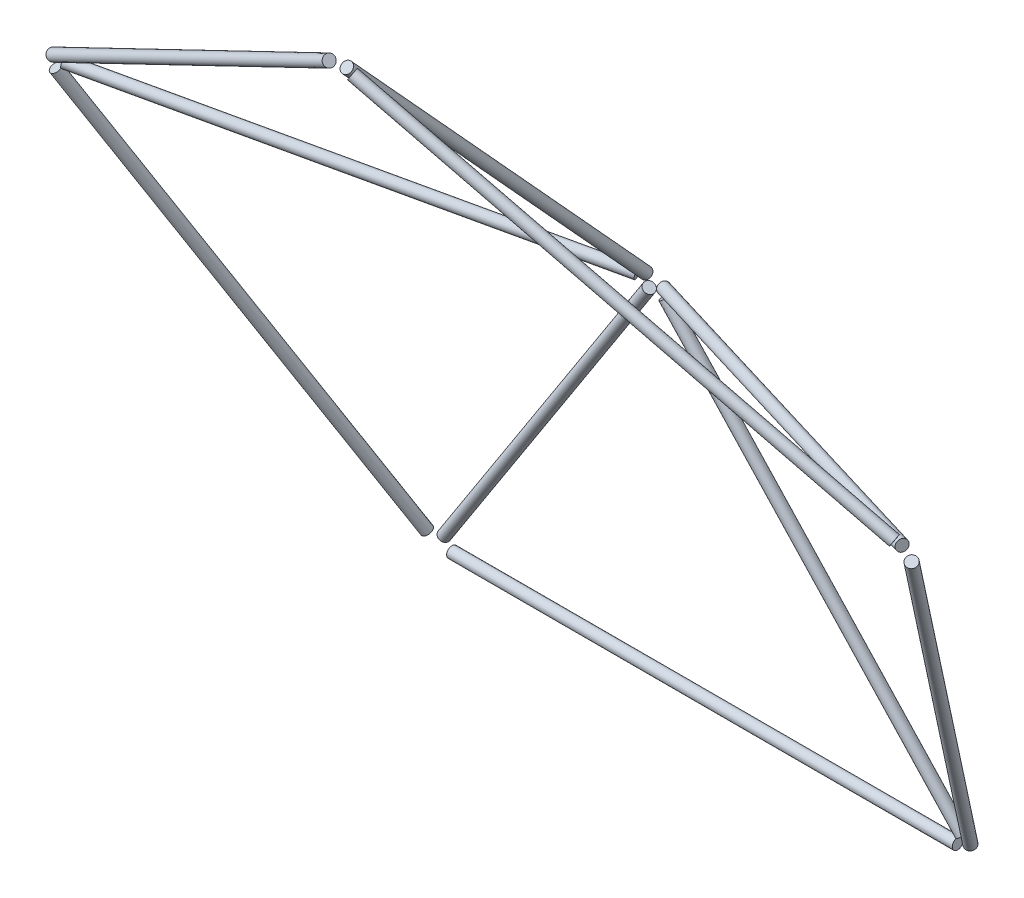
SolidWorks part; units mm, degrees
note: '?' marks a value the reader was unsure of.
ref_plane "Front Plane" through (0, 0, 0) normal (0, 0, 1) x (1, 0, 0)
ref_plane "Top Plane" through (0, 0, 0) normal (0, 1, 0) x (1, 0, 0)
ref_plane "Right Plane" through (0, 0, 0) normal (1, 0, 0) x (0, 0, -1)
sketch "Sketch1" plane through (0, 0, 0) normal (0, 1, 0) x (1, 0, 0)
  line L0 (190.928, 143.4196) -> (77.4001, 225.9024)
  line L1 (194.1641, -141.0685) -> (240, 0) construction
  line L2 (240, 0) -> (194.1641, 141.0685) construction
  line L3 (194.1641, 141.0685) -> (74.1641, 228.2536) construction
  line L4 (74.1641, 228.2536) -> (-74.1641, 228.2536) construction
  line L5 (-74.1641, 228.2536) -> (-194.1641, 141.0685) construction
  line L6 (-194.1641, 141.0685) -> (-240, 0) construction
  line L7 (-240, 0) -> (-194.1641, -141.0685) construction
  line L8 (-194.1641, -141.0685) -> (-74.1641, -228.2536) construction
  line L9 (-74.1641, -228.2536) -> (74.1641, -228.2536) construction
  line L10 (74.1641, -228.2536) -> (194.1641, -141.0685) construction
  line L11 (120, 87.1851) -> (74.1641, 228.2536) construction
  line L12 (74.1641, 228.2536) -> (-74.1641, 228.2536) construction
  line L13 (-74.1641, 228.2536) -> (-120, 87.1851) construction
  line L14 (-120, 87.1851) -> (0, 0) construction
  line L15 (0, 0) -> (120, 87.1851) construction
  line L16 (0, 0) -> (-194.1641, -141.0685) construction
  line L17 (-74.1641, -228.2536) -> (74.1641, 228.2536) construction
  circle A0 centre (0, 0) radius 240 construction
  circle A1 centre (0, 0) radius 228.2536 construction
  circle A2 centre (0, 126.1755) radius 102.0781 construction
  point P16 (0, 240)
  point P24 (0, 228.2536)
  dimension "D1" = 480
  dimension "D2" = 4
  dimension "D3" = 4
sketch "Sketch5" plane through (0, 0, 0) normal (1, 0, 0) x (0, 0, -1)
  line L0 (0, 0) -> (126.1755, 204.1562)
  line L1 (126.1755, 204.1562) -> (228.2536, 0)
  line L2 (182.6029, 91.3014) -> (214.6625, 107.3313) construction
  line L3 (-49.7754, 154.1978) -> (144.5877, 34.0748) construction
  circle A0 centre (228.2536, 0) radius 228.2536 construction
  circle A1 centre (0, 0) radius 240 construction
  circle A2 centre (228.2536, 0) radius 102.0781 construction
  point P0 (228.2536, 0)
  point P8 (126.1755, 204.1562)
ref_plane "Plane1" through (0, 91.3014, -182.6029) normal (0, 0.4472, -0.8944) x (-1, 0, 0)
sketch "Sketch6" plane through (0, 91.3014, -182.6029) normal (0, 0.4472, -0.8944) x (-1, 0, 0)
  line L0 (-74.1641, -102.0781) -> (74.1641, -102.0781) construction
  line L1 (-74.1641, -102.0781) -> (74.1641, -102.0781)
  line L2 (-118.7639, 35.1861) -> (-75.4001, -98.2739)
  line L3 (-74.1641, -102.0781) -> (74.1641, -102.0781)
  line L4 (74.1641, -102.0781) -> (120, 38.9904)
  line L5 (120, 38.9904) -> (0, 126.1755)
  line L6 (0, 126.1755) -> (-120, 38.9904)
  line L7 (-120, 38.9904) -> (-74.1641, -102.0781) construction
  circle A0 centre (0, 0) radius 102.0781 construction
  point P0 (0, 0)
  dimension "D1" = 4
  dimension "D2" = 4
ref_plane "Plane2" through (0, 107.3313, -214.6625) normal (0, 0.4472, -0.8944) x (-1, 0, 0)
sketch "Sketch7" plane through (0, 107.3313, -214.6625) normal (0, 0.4472, -0.8944) x (-1, 0, 0)
  point P0 (0, 0)
ref_plane "Plane7" through (44.0977, 149.8374, -163.9562) normal (0.1947, 0.6617, -0.724) x (-0.9809, 0.1314, -0.1438)
sketch "Sketch15" plane through (44.0977, 149.8374, -163.9562) normal (0.1947, 0.6617, -0.724) x (-0.9809, 0.1314, -0.1438)
  line L0 (-77.3838, -18.2827) -> (44.9584, -65.584)
  line L1 (44.9584, -65.584) -> (44.9584, 65.584)
  line L2 (44.9584, 65.584) -> (-77.3838, -18.2827)
surface "Surface-Plane1" sketch "Sketch15"
ref_plane "Plane8" through (71.3515, 74.814, -201.4679) normal (0.3151, 0.3304, -0.8897) x (-0.9491, 0.1097, -0.2954)
sketch "Sketch16" plane through (71.3515, 74.814, -201.4679) normal (0.3151, 0.3304, -0.8897) x (-0.9491, 0.1097, -0.2954)
  line L0 (-2.9635, -79.459) -> (75.1812, 25.8901) construction
  line L1 (72.7982, 22.6774) -> (-0.5805, -76.2463)
  dimension "D1" = 4
  dimension "D2" = 4
ref_axis "Axis2" through (0, 91.3014, -182.6029) along (0, 0.4472, -0.8944)?
ref_axis "Axis3" through (0, -137.2552, 0) along (0, 1, 0)?
pattern_circular "CirPattern4" count 5 over 360 about axis through (0, 91.3014, -182.6029) along (0, 0.4472, -0.8944)
pattern_circular "CirPattern5" count 5 over 360 about axis through (0, 0, 0) along (0, 1, 0)
ref_plane "Plane11" through (129.4427, 42.0585, -178.1626) normal (0.5774, 0.1876, -0.7947) x (-0.8165, 0.1326, -0.5619)
pattern_circular "CirPattern6" [suppressed] count 5 over 360 about axis through (0, -137.2552, 0) along (0, 1, 0)
ref_plane "Plane12" through (0, 0, 0) normal (0, -0.5257, -0.8507) x (-1, 0, 0)
mirror "Mirror1" about plane through (0, 0, 0) normal (0, -0.5257, -0.8507)
ref_axis "Axis1" through (0, 107.8975, 0) along (0, -1, 0)?
ref_plane "Plane13" through (2.2617, 104.0582, -215.077) normal (0.5654, -0.8183, -0.1036) x (-0.8248, -0.5609, -0.071)
sketch "Sketch20" plane through (2.2617, 104.0582, -215.077) normal (0.5654, -0.8183, -0.1036) x (-0.8248, -0.5609, -0.071)
  circle A0 centre (0, 0) radius 1.5
  dimension "D1" = 3
sweep "Sweep4" add profiles "Sketch20" path "Sketch16"
ref_plane "Plane14" through (75.4001, 3.4026, -226.5523) normal (-0.309, -0.8507, -0.4253) x (-0.9511, 0.2764, 0.1382)
sketch "Sketch21" plane through (75.4001, 3.4026, -226.5523) normal (-0.309, -0.8507, -0.4253) x (-0.9511, 0.2764, 0.1382)
  circle A0 centre (0, 0) radius 1.5
  dimension "D1" = 3
sweep "Sweep5" add profiles "Sketch21" path "Sketch6"
pattern_circular "CirPattern7" count 5 over 360 about axis through (0, 91.3014, -182.6029) along (0, 0.4472, -0.8944) of bodies 167
pattern_circular "CirPattern8" count 5 over 360 about axis through (0, 0, 0) along (0, 0.4472, -0.8944) of bodies 168
ref_plane "Plane15" through (77.4001, 0, -225.9024) normal (-0.809, 0, -0.5878) x (-0.5878, 0, 0.809)
sketch "Sketch22" plane through (77.4001, 0, -225.9024) normal (-0.809, 0, -0.5878) x (-0.5878, 0, 0.809)
  circle A0 centre (0, 0) radius 1.5
  dimension "D1" = 3
sketch "Sketch23" plane through (0, 0, 0) normal (0, 1, 0) x (1, 0, 0)
  line L0 (-210, 0) -> (-169.8936, -123.4349)
  line L1 (169.8936, -123.4349) -> (210, 0)
  line L2 (210, 0) -> (169.8936, 123.4349)
  line L3 (169.8936, 123.4349) -> (64.8936, 199.7219)
  line L4 (64.8936, 199.7219) -> (-64.8936, 199.7219)
  line L5 (-64.8936, 199.7219) -> (-169.8936, 123.4349)
  line L6 (-169.8936, 123.4349) -> (-210, 0)
  line L7 (-169.8936, -123.4349) -> (-64.8936, -199.7219)
  line L8 (-64.8936, -199.7219) -> (64.8936, -199.7219)
  line L9 (64.8936, -199.7219) -> (169.8936, -123.4349)
  circle A0 centre (0, 0) radius 199.7219 construction
  dimension "D1" = 420
